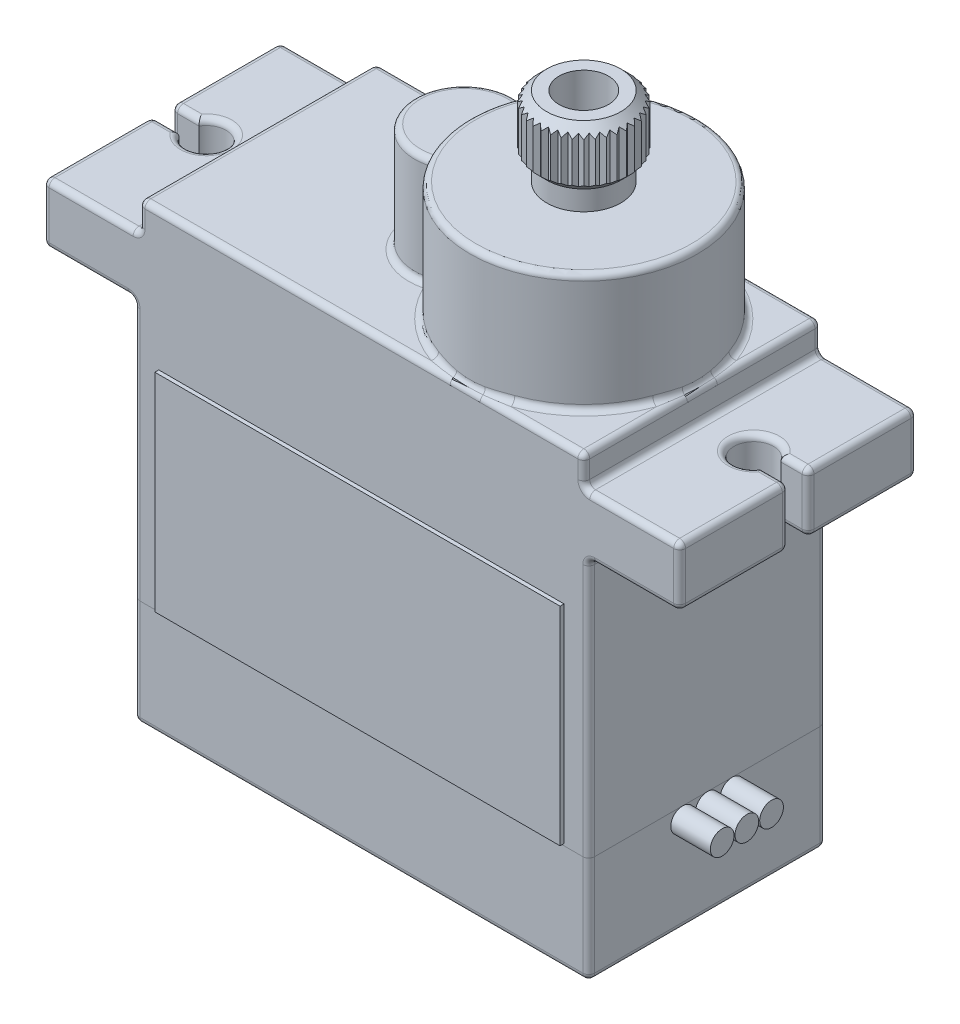
SolidWorks part; units mm, degrees
ref_plane "Front Plane" through (0, 0, 0) normal (0, 0, 1) x (1, 0, 0)
ref_plane "Top Plane" through (0, 0, 0) normal (0, 1, 0) x (1, 0, 0)
ref_plane "Right Plane" through (0, 0, 0) normal (1, 0, 0) x (0, 0, -1)
sketch "Sketch1" plane through (0, 0, 0) normal (0, 1, 0) x (1, 0, 0)
  line L1 (-11.5, -6) -> (11.5, -6)
  line L2 (-11.5, -6) -> (-11.5, 6)
  line L3 (-11.5, 6) -> (11.5, 6)
  line L4 (11.5, -6) -> (11.5, 6)
  line L5 (-11.5, -6) -> (11.5, 6) construction
  line L6 (-11.5, 6) -> (11.5, -6) construction
  point P0 (0, 0)
  dimension "D1" = 12
  dimension "D2" = 23
extrude "Boss-Extrude1" add sketch "Sketch1" along normal blind 18.5
sketch "Sketch2" plane through (0, 18.5, 0) normal (0, 1, 0) x (1, 0, 0)
  line L0 (11.5, 6) -> (-11.5, 6) construction
  line L1 (-16.1, -6) -> (16.1, -6)
  line L2 (-16.1, -6) -> (-16.1, 6)
  line L3 (-16.1, 6) -> (16.1, 6)
  line L4 (16.1, -6) -> (16.1, 6)
  line L5 (-16.1, -6) -> (16.1, 6) construction
  line L6 (-16.1, 6) -> (16.1, -6) construction
  point P0 (0, 0)
  dimension "D1" = 32.2
extrude "Boss-Extrude2" add sketch "Sketch2" along normal blind 3
sketch "Sketch3" plane through (0, 21.5, 0) normal (0, 1, 0) x (1, 0, 0)
  line L0 (16.1, 6) -> (-16.1, 6) construction
  line L1 (-11.25, -6) -> (11.25, -6)
  line L2 (-11.25, -6) -> (-11.25, 6)
  line L3 (-11.25, 6) -> (11.25, 6)
  line L4 (11.25, -6) -> (11.25, 6)
  line L5 (-11.25, -6) -> (11.25, 6) construction
  line L6 (-11.25, 6) -> (11.25, -6) construction
  point P0 (0, 0)
  dimension "D1" = 22.5
extrude "Boss-Extrude3" add sketch "Sketch3" along normal blind 1.5
sketch "Sketch4" plane through (0, 23, 0) normal (0, 1, 0) x (1, 0, 0)
  line L0 (-11.25, 6) -> (-11.25, -6) construction
  line L1 (5.25, 5.75) -> (5.25, 6) construction
  line L2 (11.25, 6) -> (-11.25, 6) construction
  line L3 (11, 0) -> (11.25, 0) construction
  line L4 (11.25, -6) -> (11.25, 6) construction
  line L5 (5.25, -5.75) -> (5.25, -6) construction
  line L6 (-11.25, -6) -> (11.25, -6) construction
  circle A0 centre (5.25, 0) radius 5.75
  point P5 (-11.25, 0)
  dimension "D1" = 11.5
extrude "Boss-Extrude4" add sketch "Sketch4" along normal blind 6
sketch "Sketch5" plane through (0, 23, 0) normal (0, 1, 0) x (1, 0, 0)
  line L0 (-11.25, 6) -> (-11.25, -6) construction
  circle A0 centre (-0.8, 0) radius 2.5
  circle A1 centre (5.25, 0) radius 5.75 construction
  circle A2 centre (5.25, 0) radius 5.75 construction
  point P2 (-3.3, 0)
  point P5 (-11.25, 0)
  point P6 (11, 0)
  dimension "D1" = 5
  dimension "D2" = 14.3
extrude "Boss-Extrude5" add sketch "Sketch5" along normal blind 5.5
sketch "Sketch6" plane through (0, 21.5, 0) normal (0, 1, 0) x (1, 0, 0)
  line L0 (-11.25, 6) -> (-11.25, -6) construction
  line L1 (0, 6) -> (0, -6) construction
  line L2 (11.25, 6) -> (-11.25, 6) construction
  line L3 (-11.25, -6) -> (11.25, -6) construction
  line L4 (-14.716, 0.5) -> (-16.1, 0.5)
  line L5 (-16.1, 6) -> (-16.1, -6) construction
  line L6 (-14.716, -0.5) -> (-16.1, -0.5)
  line L7 (-16.1, 0.5) -> (-16.1, -0.5)
  line L8 (16.1, 0.5) -> (16.1, -0.5)
  line L9 (14.716, -0.5) -> (16.1, -0.5)
  line L10 (14.716, 0.5) -> (16.1, 0.5)
  arc A0 (-14.716, -0.5) -> (-14.716, 0.5) centre (-13.85, 0) ccw
  arc A1 (14.716, -0.5) -> (14.716, 0.5) centre (13.85, 0) cw
  point P4 (-11.25, 0)
  dimension "D1" = 2
  dimension "D2" = 27.7
  dimension "D3" = 1
extrude "Cut-Extrude1" cut sketch "Sketch6" against normal through all
sketch "Sketch7" plane through (0, 29, 0) normal (0, 1, 0) x (1, 0, 0)
  circle A0 centre (5.25, 0) radius 2.375
  dimension "D1" = 4.75
extrude "Boss-Extrude6" add sketch "Sketch7" along normal blind 4
sketch "Sketch8" plane through (11.5, 0, 0) normal (1, 0, 0) x (0, 0, -1)
  line L0 (-1.25, 4.8) -> (1.25, 4.8) construction
  line L1 (-6, 0) -> (6, 0) construction
  circle A0 centre (-1.25, 4.8) radius 0.6
  circle A1 centre (0, 4.8) radius 0.6
  circle A2 centre (1.25, 4.8) radius 0.6
  dimension "D1" = 1.2
  dimension "D2" = 4.8
  dimension "D3" = 2.5
extrude "Boss-Extrude8" add sketch "Sketch8" along normal blind 2
fillet "Fillet1" radius 0.3 56 edges at (11.5, 0, 0) (11.5, 18.5, 0) (15.408, 18.5, 0.5) (12.85, 18.5, 0) (15.408, 18.5, -0.5) (15.408, 21.5, 0.5) (15.408, 21.5, -0.5) (12.85, 21.5, 0) (-11.25, 23, 0) (-15.408, 21.5, -0.5) (-11.25, 21.5, 0) (-15.408, 21.5, 0.5) (-12.85, 21.5, 0) (-16.1, 20, 0.5) (-16.1, 21.5, 3.25) (-16.1, 21.5, -3.25) (-16.1, 20, -0.5) (-16.1, 18.5, 3.25) (-16.1, 18.5, -3.25) (-15.408, 18.5, -0.5) (-12.85, 18.5, 0) (-15.408, 18.5, 0.5) (-11.5, 18.5, 0) (-11.5, 0, 0) (11.25, 23, 0) (11.25, 21.5, 0) (16.1, 21.5, 3.25) (16.1, 20, 0.5) (16.1, 18.5, 3.25) (16.1, 18.5, -3.25) (16.1, 20, -0.5) (16.1, 21.5, -3.25) (11.5, 9.25, -6) (13.8, 18.5, -6) (16.1, 20, -6) (13.675, 21.5, -6) (11.25, 22.25, -6) (0, 23, -6) (-11.25, 22.25, -6) (-13.675, 21.5, -6) (-16.1, 20, -6) (-13.8, 18.5, -6) (-11.5, 9.25, -6) (0, 0, -6) (-11.5, 9.25, 6) (-13.8, 18.5, 6) (-16.1, 20, 6) (-13.675, 21.5, 6) (-11.25, 22.25, 6) (0, 23, 6) (11.25, 22.25, 6) (13.675, 21.5, 6) (16.1, 20, 6) (13.8, 18.5, 6) (11.5, 9.25, 6) (0, 0, 6)
fillet "Fillet2" radius 0.3 10 edges at (5.25, 23, 5.75) (9.3159, 23, 4.0659) (11, 23, 0) (9.3159, 23, -4.0659) (5.25, 23, -5.75) (-3.3, 23, 0) (1.8189, 23, 4.6141) (1.8189, 23, -4.6141) (5.25, 29, 5.75) (-3.3, 28.5, 0)
chamfer "Chamfer1" distance 0.5 angle 45 1 edges at (5.25, 33, 2.375)
sketch "Sketch10" plane through (0, 33, 0) normal (0, 1, 0) x (1, 0, 0)
  line L0 (5.25, 0) -> (5.043, 2.366) construction
  line L1 (5.25, 0) -> (5.457, 2.366) construction
  line L2 (5.25, 0) -> (5.25, 2.375) construction
  line L3 (5.043, 2.366) -> (5.25, 2.2)
  line L4 (5.25, 2.2) -> (5.457, 2.366)
  line L5 (5.632, 2.1666) -> (5.8647, 2.2941)
  line L6 (5.457, 2.366) -> (5.632, 2.1666)
  line L7 (6.0024, 2.0673) -> (6.2537, 2.1525)
  line L8 (5.8647, 2.2941) -> (6.0024, 2.0673)
  line L9 (6.35, 1.9053) -> (6.6122, 1.9455)
  line L10 (6.2537, 2.1525) -> (6.35, 1.9053)
  line L11 (6.6641, 1.6853) -> (6.9294, 1.6794)
  line L12 (6.6122, 1.9455) -> (6.6641, 1.6853)
  line L13 (6.9353, 1.4141) -> (7.1955, 1.3622)
  line L14 (6.9294, 1.6794) -> (6.9353, 1.4141)
  line L15 (7.1553, 1.1) -> (7.4025, 1.0037)
  line L16 (7.1955, 1.3622) -> (7.1553, 1.1)
  line L17 (7.3173, 0.7524) -> (7.5441, 0.6147)
  line L18 (7.4025, 1.0037) -> (7.3173, 0.7524)
  line L19 (7.4166, 0.382) -> (7.616, 0.207)
  line L20 (7.5441, 0.6147) -> (7.4166, 0.382)
  line L21 (7.45, 0) -> (7.616, -0.207)
  line L22 (7.616, 0.207) -> (7.45, 0)
  line L23 (7.4166, -0.382) -> (7.5441, -0.6147)
  line L24 (7.616, -0.207) -> (7.4166, -0.382)
  line L25 (7.3173, -0.7524) -> (7.4025, -1.0037)
  line L26 (7.5441, -0.6147) -> (7.3173, -0.7524)
  line L27 (7.1553, -1.1) -> (7.1955, -1.3622)
  line L28 (7.4025, -1.0037) -> (7.1553, -1.1)
  line L29 (6.9353, -1.4141) -> (6.9294, -1.6794)
  line L30 (7.1955, -1.3622) -> (6.9353, -1.4141)
  line L31 (6.6641, -1.6853) -> (6.6122, -1.9455)
  line L32 (6.9294, -1.6794) -> (6.6641, -1.6853)
  line L33 (6.35, -1.9053) -> (6.2537, -2.1525)
  line L34 (6.6122, -1.9455) -> (6.35, -1.9053)
  line L35 (6.0024, -2.0673) -> (5.8647, -2.2941)
  line L36 (6.2537, -2.1525) -> (6.0024, -2.0673)
  line L37 (5.632, -2.1666) -> (5.457, -2.366)
  line L38 (5.8647, -2.2941) -> (5.632, -2.1666)
  line L39 (5.25, -2.2) -> (5.043, -2.366)
  line L40 (5.457, -2.366) -> (5.25, -2.2)
  line L41 (4.868, -2.1666) -> (4.6353, -2.2941)
  line L42 (5.043, -2.366) -> (4.868, -2.1666)
  line L43 (4.4976, -2.0673) -> (4.2463, -2.1525)
  line L44 (4.6353, -2.2941) -> (4.4976, -2.0673)
  line L45 (4.15, -1.9053) -> (3.8878, -1.9455)
  line L46 (4.2463, -2.1525) -> (4.15, -1.9053)
  line L47 (3.8359, -1.6853) -> (3.5706, -1.6794)
  line L48 (3.8878, -1.9455) -> (3.8359, -1.6853)
  line L49 (3.5647, -1.4141) -> (3.3045, -1.3622)
  line L50 (3.5706, -1.6794) -> (3.5647, -1.4141)
  line L51 (3.3447, -1.1) -> (3.0975, -1.0037)
  line L52 (3.3045, -1.3622) -> (3.3447, -1.1)
  line L53 (3.1827, -0.7524) -> (2.9559, -0.6147)
  line L54 (3.0975, -1.0037) -> (3.1827, -0.7524)
  line L55 (3.0834, -0.382) -> (2.884, -0.207)
  line L56 (2.9559, -0.6147) -> (3.0834, -0.382)
  line L57 (3.05, 0) -> (2.884, 0.207)
  line L58 (2.884, -0.207) -> (3.05, 0)
  line L59 (3.0834, 0.382) -> (2.9559, 0.6147)
  line L60 (2.884, 0.207) -> (3.0834, 0.382)
  line L61 (3.1827, 0.7524) -> (3.0975, 1.0037)
  line L62 (2.9559, 0.6147) -> (3.1827, 0.7524)
  line L63 (3.3447, 1.1) -> (3.3045, 1.3622)
  line L64 (3.0975, 1.0037) -> (3.3447, 1.1)
  line L65 (3.5647, 1.4141) -> (3.5706, 1.6794)
  line L66 (3.3045, 1.3622) -> (3.5647, 1.4141)
  line L67 (3.8359, 1.6853) -> (3.8878, 1.9455)
  line L68 (3.5706, 1.6794) -> (3.8359, 1.6853)
  line L69 (4.15, 1.9053) -> (4.2463, 2.1525)
  line L70 (3.8878, 1.9455) -> (4.15, 1.9053)
  line L71 (4.4976, 2.0673) -> (4.6353, 2.2941)
  line L72 (4.2463, 2.1525) -> (4.4976, 2.0673)
  line L73 (4.868, 2.1666) -> (5.043, 2.366)
  line L74 (4.6353, 2.2941) -> (4.868, 2.1666)
  circle A0 centre (5.25, 0) radius 2.375 construction
  arc A1 (5.457, 2.366) -> (5.043, 2.366) centre (5.25, 0) ccw
  circle A2 centre (5.25, 0) radius 2.2 construction
  arc A3 (5.8647, 2.2941) -> (5.457, 2.366) centre (5.25, 0) ccw
  arc A4 (6.2537, 2.1525) -> (5.8647, 2.2941) centre (5.25, 0) ccw
  arc A5 (6.6122, 1.9455) -> (6.2537, 2.1525) centre (5.25, 0) ccw
  arc A6 (6.9294, 1.6794) -> (6.6122, 1.9455) centre (5.25, 0) ccw
  arc A7 (7.1955, 1.3622) -> (6.9294, 1.6794) centre (5.25, 0) ccw
  arc A8 (7.4025, 1.0037) -> (7.1955, 1.3622) centre (5.25, 0) ccw
  arc A9 (7.5441, 0.6147) -> (7.4025, 1.0037) centre (5.25, 0) ccw
  arc A10 (7.616, 0.207) -> (7.5441, 0.6147) centre (5.25, 0) ccw
  arc A11 (7.616, -0.207) -> (7.616, 0.207) centre (5.25, 0) ccw
  arc A12 (7.5441, -0.6147) -> (7.616, -0.207) centre (5.25, 0) ccw
  arc A13 (7.4025, -1.0037) -> (7.5441, -0.6147) centre (5.25, 0) ccw
  arc A14 (7.1955, -1.3622) -> (7.4025, -1.0037) centre (5.25, 0) ccw
  arc A15 (6.9294, -1.6794) -> (7.1955, -1.3622) centre (5.25, 0) ccw
  arc A16 (6.6122, -1.9455) -> (6.9294, -1.6794) centre (5.25, 0) ccw
  arc A17 (6.2537, -2.1525) -> (6.6122, -1.9455) centre (5.25, 0) ccw
  arc A18 (5.8647, -2.2941) -> (6.2537, -2.1525) centre (5.25, 0) ccw
  arc A19 (5.457, -2.366) -> (5.8647, -2.2941) centre (5.25, 0) ccw
  arc A20 (5.043, -2.366) -> (5.457, -2.366) centre (5.25, 0) ccw
  arc A21 (4.6353, -2.2941) -> (5.043, -2.366) centre (5.25, 0) ccw
  arc A22 (4.2463, -2.1525) -> (4.6353, -2.2941) centre (5.25, 0) ccw
  arc A23 (3.8878, -1.9455) -> (4.2463, -2.1525) centre (5.25, 0) ccw
  arc A24 (3.5706, -1.6794) -> (3.8878, -1.9455) centre (5.25, 0) ccw
  arc A25 (3.3045, -1.3622) -> (3.5706, -1.6794) centre (5.25, 0) ccw
  arc A26 (3.0975, -1.0037) -> (3.3045, -1.3622) centre (5.25, 0) ccw
  arc A27 (2.9559, -0.6147) -> (3.0975, -1.0037) centre (5.25, 0) ccw
  arc A28 (2.884, -0.207) -> (2.9559, -0.6147) centre (5.25, 0) ccw
  arc A29 (2.884, 0.207) -> (2.884, -0.207) centre (5.25, 0) ccw
  arc A30 (2.9559, 0.6147) -> (2.884, 0.207) centre (5.25, 0) ccw
  arc A31 (3.0975, 1.0037) -> (2.9559, 0.6147) centre (5.25, 0) ccw
  arc A32 (3.3045, 1.3622) -> (3.0975, 1.0037) centre (5.25, 0) ccw
  arc A33 (3.5706, 1.6794) -> (3.3045, 1.3622) centre (5.25, 0) ccw
  arc A34 (3.8878, 1.9455) -> (3.5706, 1.6794) centre (5.25, 0) ccw
  arc A35 (4.2463, 2.1525) -> (3.8878, 1.9455) centre (5.25, 0) ccw
  arc A36 (4.6353, 2.2941) -> (4.2463, 2.1525) centre (5.25, 0) ccw
  arc A37 (5.043, 2.366) -> (4.6353, 2.2941) centre (5.25, 0) ccw
  point P114 (5.25, 0)
  dimension "D1" = 4.4
  dimension "D2" = 10
  dimension "D3" = 36
extrude "Cut-Extrude2" cut sketch "Sketch10" against normal up to surface (4 mm away) contours L69 A35 L70 | L67 A34 L68 | L65 A33 L66 | L63 A32 L64 | L61 A31 L62 | L59 A30 L60 | L57 A29 L58 | L55 A28 L56 | L53 A27 L54 | L51 A26 L52 | L49 A25 L50 | L45 A23 L46 | L43 A22 L44 | L41 A21 L42 | L39 A20 L40 | L37 A19 L38 | L35 A18 L36 | L33 A17 L34 | L31 A16 L32 | L29 A15 L30 | L27 A14 L28 | L25 A13 L26 | L23 A12 L24 | L21 A11 L22 | L19 A10 L20 | L17 A9 L18 | L15 A8 L16 | L13 A7 L14 | L11 A6 L12 | L9 A5 L10 | L7 A4 L8 | L5 A3 L6 | L4 A1 L3 | L73 A37 L74 | L71 A36 L72 | L47 A24 L48 region at (5.25, 33, -2.3146) region at (4.8481, 33, -2.2795) region at (5.6519, 33, -2.2795) region at (4.4583, 33, -2.175) region at (6.0417, 33, -2.175) region at (4.0927, 33, -2.0045) region at (6.4073, 33, -2.0045) region at (3.7622, 33, -1.7731) region at (6.7378, 33, -1.7731) region at (3.4769, 33, -1.4878) region at (7.0231, 33, -1.4878) region at (3.2455, 33, -1.1573) region at (7.2545, 33, -1.1573) region at (3.075, 33, -0.7917) region at (7.425, 33, -0.7917) region at (2.9705, 33, -0.4019) region at (7.5295, 33, -0.4019) region at (2.9354, 33, 0) region at (7.5646, 33, 0) region at (2.9705, 33, 0.4019) region at (7.5295, 33, 0.4019) region at (3.075, 33, 0.7917) region at (7.425, 33, 0.7917) region at (3.2455, 33, 1.1573) region at (7.2545, 33, 1.1573) region at (3.4769, 33, 1.4878) region at (7.0231, 33, 1.4878) region at (6.7378, 33, 1.7731) region at (4.0927, 33, 2.0045) region at (6.4073, 33, 2.0045) region at (4.4583, 33, 2.175) region at (6.0417, 33, 2.175) region at (4.8481, 33, 2.2795) region at (5.6519, 33, 2.2795) region at (5.25, 33, 2.3146) up to face at (5.25, 29, 5.45)
sketch "Sketch11" plane through (0, 0, 0) normal (0, 0, 1) x (1, 0, 0)
  line L0 (5.25, 33) -> (5.25, 27.5426) construction
  line L1 (7.816, 29) -> (7.216, 29)
  line L2 (7.816, 29) -> (7.816, 29.3)
  line L3 (7.816, 29.3) -> (7.216, 29.3)
  line L4 (7.216, 29) -> (7.216, 29.3)
  line L5 (7.125, 33) -> (3.375, 33) construction
  line L7 (10.7, 29) -> (-0.2, 29) construction
  line L8 (7.616, 29) -> (7.616, 32.5) construction
  dimension "D1" = 0.3
  dimension "D2" = 0.4
  dimension "D3" = 0.2
revolve "Cut-Revolve1" cut sketch "Sketch11" angle 360 about L0 other way angle 360
sketch "Sketch12" plane through (0, 0, 6) normal (0, 0, 1) x (1, 0, 0)
  line L0 (11.2, 0) -> (-11.2, 0) construction
  line L1 (-10.25, 5.5) -> (10.25, 5.5)
  line L2 (-10.25, 5.5) -> (-10.25, 16)
  line L3 (-10.25, 16) -> (10.25, 16)
  line L4 (10.25, 5.5) -> (10.25, 16)
  line L5 (-10.25, 5.5) -> (10.25, 16) construction
  line L6 (-10.25, 16) -> (10.25, 5.5) construction
  point P0 (0, 10.75)
  dimension "D1" = 10.5
  dimension "D2" = 20.5
  dimension "D3" = 5.5
extrude "Boss-Extrude9" add sketch "Sketch12" along normal blind 0.2
sketch "Sketch13" plane through (0, 0, -6) normal (0, 0, -1) x (-1, 0, 0)
  line L4 (-10.25, 16) -> (-10.25, 5.5)
  line L5 (10.25, 16) -> (-10.25, 16)
  line L6 (10.25, 5.5) -> (10.25, 16)
  line L7 (-10.25, 5.5) -> (10.25, 5.5)
  line L8 (-10.25, 16) -> (-10.25, 5.5)
  line L9 (10.25, 16) -> (-10.25, 16)
  line L10 (10.25, 5.5) -> (10.25, 16)
  line L11 (-10.25, 5.5) -> (10.25, 5.5)
  dimension "D1" = 0
extrude "Boss-Extrude10" add sketch "Sketch13" along normal blind 0.2
ref_plane "Plane1" through (0, 5.4, 0) normal (0, 1, 0) x (1, 0, 0)
split line "Split Line1"
sketch "Sketch14" plane through (0, 33, 0) normal (0, 1, 0) x (1, 0, 0)
  circle A0 centre (5.25, 0) radius 1.25
  dimension "D1" = 2.5
extrude "Cut-Extrude3" cut sketch "Sketch14" against normal blind 2.5
ref_axis "Axis1" through (5.25, 30.5, 0) along (0, 1, 0)
ref_plane "Plane2" through (0, 0, 0) normal (0, 0, 1) x (1, 0, 0)
sketch "Sketch15" plane through (0, 0, 0) normal (0, 0, 1) x (1, 0, 0)
  line L0 (7.125, 30) -> (3.375, 30) construction
  line L2 (7.125, 33) -> (3.375, 33) construction
  line L3 (7.125, 33) -> (3.375, 33) construction
  line L4 (3.375, 30) -> (1.884, 31.491)
  line L5 (3.375, 30) -> (1.884, 30) construction
  line L6 (1.884, 30) -> (1.884, 31.491)
  line L7 (10.7, 29) -> (-0.2, 29) construction
  line L8 (10.7, 29) -> (-0.2, 29) construction
  line L9 (3.375, 30) -> (3.375, 29)
  line L10 (3.375, 29) -> (1.884, 29)
  line L11 (1.884, 29) -> (1.884, 30)
  line L12 (10.7, 29) -> (-0.2, 29) construction
  point P9 (1.7595, 29.4341)
  dimension "D1" = 45
  dimension "D2" = 1
  dimension "D3" = 1
revolve "Cut-Revolve2" cut sketch "Sketch15" angle 360 about axis through (5.25, 30.5, 0) along (0, 1, 0)
